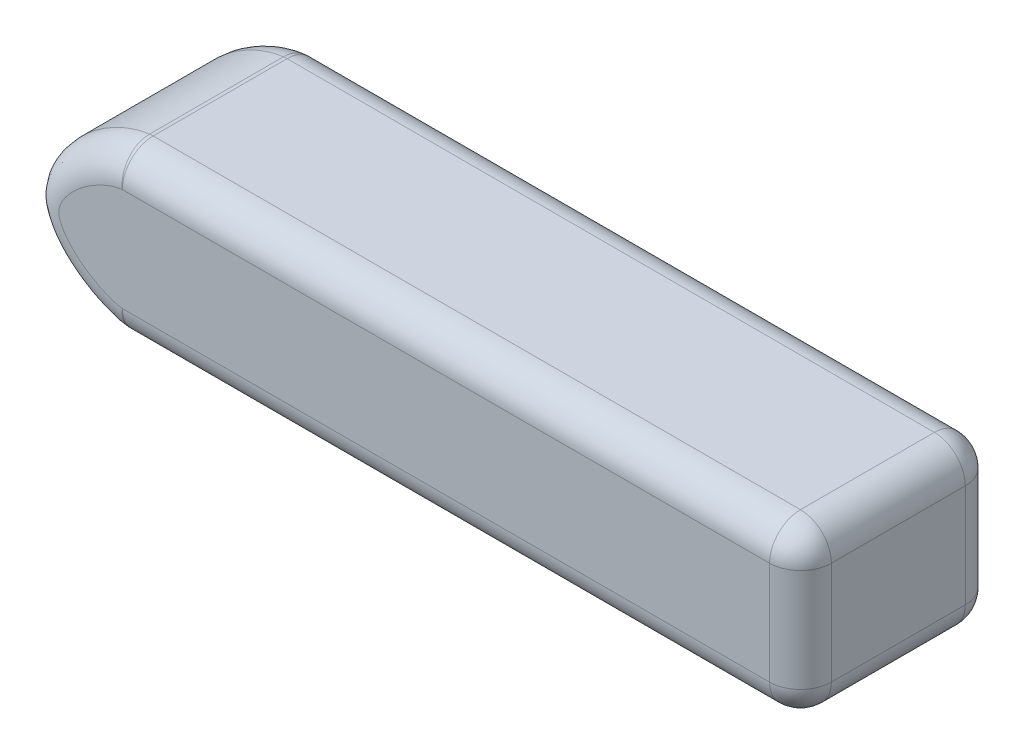
SolidWorks part; units mm, degrees
ref_plane "Front Plane" through (0, 0, 0) normal (0, 0, 1) x (1, 0, 0)
ref_plane "Top Plane" through (0, 0, 0) normal (0, 1, 0) x (1, 0, 0)
ref_plane "Right Plane" through (0, 0, 0) normal (1, 0, 0) x (0, 0, -1)
sketch "Sketch1" plane through (0, 0, 0) normal (0, 1, 0) x (1, 0, 0)
  line L1 (-37.5, 9.5) -> (37.5, 9.5)
  line L2 (-37.5, 9.5) -> (-37.5, -9.5)
  line L3 (-37.5, -9.5) -> (37.5, -9.5)
  line L4 (37.5, 9.5) -> (37.5, -9.5)
  line L5 (-37.5, 9.5) -> (37.5, -9.5) construction
  line L6 (-37.5, -9.5) -> (37.5, 9.5) construction
  point P0 (0, 0)
  dimension "D1" = 75
  dimension "D2" = 19
extrude "Boss-Extrude1" add sketch "Sketch1" along normal mid plane 16
sketch "Sketch2" plane through (0, 0, -9.5) normal (0, 0, -1) x (-1, 0, 0)
  line L0 (-37.5, 0) -> (37.5, 0) construction
  line L1 (-37.5, 8) -> (-37.5, -8) construction
  line L2 (37.5, 8) -> (37.5, -8) construction
  line L3 (-37.5, 8) -> (37.5, 8) construction
  line L4 (-37.5, -8) -> (37.5, -8) construction
  line L5 (27.5, 8) -> (27.5, -8) construction
  line L6 (33.5, 6) -> (33.5, -6) construction
  line L7 (27.5, 8) -> (37.5, 8)
  line L8 (37.5, 8) -> (37.5, -8)
  line L9 (37.5, -8) -> (27.5, -8)
  spline S0 degree 3 poles (27.5, 8) (31.2465, 8.3701) (43.7535, 0) (31.2465, -8.3701) (27.5, -8) knots 0 0 0 0 0.5 1 1 1 1
  point P14 (33.5, 0)
  line M5 (37.5, -8) -> (37.5, 8)
  line M6 (37.5, 8) -> (-37.5, 8)
  dimension "D1" = 10
  dimension "D2" = 4
  dimension "D3" = 12
extrude "Cut-Extrude1" cut sketch "Sketch2" against normal blind 19 contours S0 L9 M5 | S0 L8 M6 region at (-35.1724, -6.0703, -9.5) region at (-35.1724, 6.0703, -9.5)
fillet "Fillet1" radius 3 12 edges at (-28.4869, 8, 0) (-28.4869, -8, 0) (37.5, 8, 0) (37.5, -8, 0) (4.5066, -8, -9.5) (37.5, 0, -9.5) (4.5066, 8, -9.5) (37.5, 0, 9.5) (4.5066, -8, 9.5) (4.5066, 8, 9.5)
